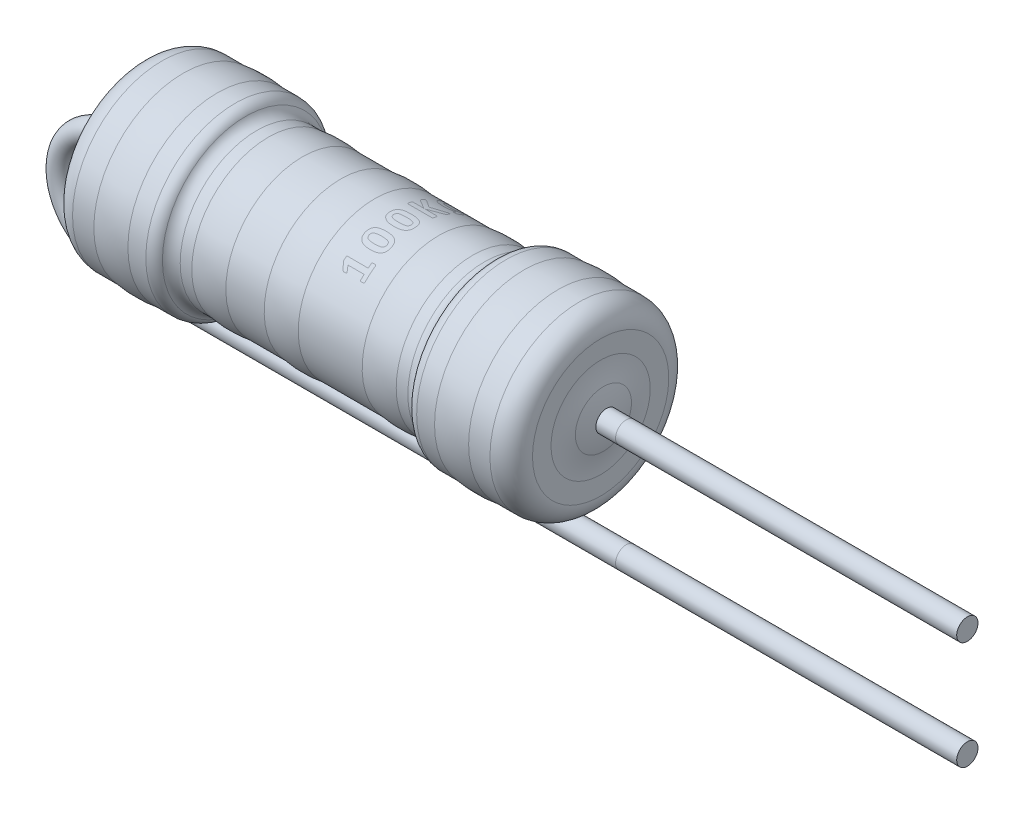
SolidWorks part; units mm, degrees
ref_plane "Front Plane" through (0, 0, 0) normal (0, 0, 1) x (1, 0, 0)
ref_plane "Top Plane" through (0, 0, 0) normal (0, 1, 0) x (1, 0, 0)
ref_plane "Right Plane" through (0, 0, 0) normal (1, 0, 0) x (0, 0, -1)
sketch "Sketch Set Wire Width" plane through (0, 0, 0) normal (0, 0, 1) x (1, 0, 0)
  line L0 (0, 0) -> (6, 0)
  line L1 (6, -2.54) -> (-6, -2.54)
  line L2 (6, 0) -> (14.0102, 0)
  line L3 (-6, 0) -> (-6, -2.54) construction
  line L4 (-6, 0) -> (-6, -2.54) construction
  line L5 (6, -2.54) -> (6, 0) construction
  line L6 (6, -2.54) -> (14.0102, -2.54)
  line L7 (14.0102, -2.54) -> (14.0102, 0) construction
  line L8 (-6, 0) -> (0, 0)
  arc A0 (-6, 0) -> (-6, -2.54) centre (-6, -1.27) ccw
  point P1 (0, 0)
  dimension "D2" = 2.54
  dimension "D3" = 30
  dimension "D1" = 12
  dimension "D4" = 6
sketch "Sketch Wire Diameter" plane through (0, 0, 0) normal (1, 0, 0) x (0, 0, -1)
  circle A0 centre (0, 0) radius 0.25
  dimension "D1" = 0.5
sweep "SET WIRE LENGTH" add profiles "Sketch Wire Diameter" path "Sketch Set Wire Width"
sketch "Sketch3" plane through (0, 0, 0) normal (0, 0, 1) x (1, 0, 0)
  line L0 (-5.4, 0) -> (5.4, 0)
  line L1 (0, 0) -> (0, 1.8) construction
  line L2 (-2.9, 1.8) -> (2.9, 1.8)
  line L3 (-5.4, 0) -> (-5.4, 1.6)
  line L4 (-4.9, 2.1) -> (-3.18, 2.1)
  line L5 (-2.9, 1.82) -> (-2.9, 1.8)
  line L6 (5.4, 0) -> (5.4, 1.6)
  line L7 (4.9, 2.1) -> (3.18, 2.1)
  line L8 (2.9, 1.82) -> (2.9, 1.8)
  arc A0 (-5.4, 1.6) -> (-4.9, 2.1) centre (-4.9, 1.6) cw
  arc A1 (5.4, 1.6) -> (4.9, 2.1) centre (4.9, 1.6) ccw
  arc A2 (-3.18, 2.1) -> (-2.9, 1.82) centre (-3.18, 1.82) cw
  arc A3 (3.18, 2.1) -> (2.9, 1.82) centre (3.18, 1.82) ccw
  dimension "D5" = 0.5
  dimension "D6" = 0.28
  dimension "D1" = 10.8
  dimension "D2" = 5.8
  dimension "D3" = 1.8
  dimension "D4" = 2.1
revolve "Revolve2" add sketch "Sketch3" angle 360 about L0
fillet "Fillet1" radius 0.3 2 edges at (2.9, 0, 1.8) (-2.9, 0, 1.8)
sketch "Sketch5" plane through (0, 0, 0) normal (0, 0, 1) x (1, 0, 0)
  line L0 (0, 0) -> (2, 0) construction
  line L1 (0, 0) -> (-0.3, 0) construction
  line L2 (-0.3, 0) -> (-2, 0) construction
  line L3 (-2, 0) -> (-4, 0) construction
  line L4 (2, 0) -> (4, 0) construction
  line L5 (-4, 0) -> (-4, 2.1) construction
  line L6 (-0.3, 0) -> (-0.3, 1.8) construction
  line L7 (-2, 0) -> (-2, 1.8) construction
  line L8 (2, 0) -> (2, 1.8) construction
  line L9 (4, 0) -> (4, 2.1) construction
  line L10 (-4, 2.1) -> (-4, 2.13) construction
  line L11 (-4.9, 2.1) -> (-3.18, 2.1) construction
  line L12 (4.9, 2.1) -> (3.18, 2.1) construction
  line L13 (-2.9, 1.8) -> (2.9, 1.8) construction
  line L14 (-2, 1.8) -> (-2, 1.83) construction
  line L17 (-4.4, 2.1) -> (-3.6, 2.1)
  line L19 (-5.4, 0) -> (5.4, 0) construction
  line L22 (-2.4, 1.8) -> (-1.6, 1.8) construction
  line L26 (-0.7, 1.8) -> (0.1, 1.8) construction
  line L30 (1.6, 1.8) -> (2.4, 1.8) construction
  line L34 (3.6, 2.1) -> (4.4, 2.1) construction
  line L36 (-0.3, 1.8) -> (-0.3, 1.83) construction
  line L37 (2, 1.8) -> (2, 1.83) construction
  line L38 (4, 2.1) -> (4, 2.13) construction
  arc A0 (-4.4, 2.1) -> (-3.6, 2.1) centre (-4, -0.5517) cw
  arc A1 (-2.4, 1.8) -> (-1.6, 1.8) centre (-2, -0.8517) cw construction
  arc A2 (-0.7, 1.8) -> (0.1, 1.8) centre (-0.3, -0.8517) cw construction
  arc A3 (1.6, 1.8) -> (2.4, 1.8) centre (2, -0.8517) cw construction
  arc A4 (3.6, 2.1) -> (4.4, 2.1) centre (4, -0.5517) cw construction
  dimension "D3" = 0.8
  dimension "D1" = 4
  dimension "D2" = 4
  dimension "D4" = 0.03
  dimension "D5" = 2
  dimension "D6" = 2
  dimension "D7" = 1.7
revolve "Band 1" add sketch "Sketch5" angle 360 about L2
sketch "Sketch8" plane through (0, 0, 0) normal (0, 0, 1) x (1, 0, 0)
  line L0 (-2.4, 1.8) -> (-1.6, 1.8) construction
  line L1 (-2.4, 1.8) -> (-1.6, 1.8)
  arc A0 (-1.6, 1.8) -> (-2.4, 1.8) centre (-2, -0.8517) ccw construction
  arc A1 (-1.6, 1.8) -> (-2.4, 1.8) centre (-2, -0.8517) ccw
revolve "Band 2" add sketch "Sketch8" angle 360 about L2
sketch "Sketch9" plane through (0, 0, 0) normal (0, 0, 1) x (1, 0, 0)
  line L0 (-0.7, 1.8) -> (0.1, 1.8) construction
  line L1 (-0.7, 1.8) -> (0.1, 1.8)
  arc A0 (0.1, 1.8) -> (-0.7, 1.8) centre (-0.3, -0.8517) ccw construction
  arc A1 (0.1, 1.8) -> (-0.7, 1.8) centre (-0.3, -0.8517) ccw
revolve "Band 3" add sketch "Sketch9" angle 360 about L2
sketch "Sketch10" plane through (0, 0, 0) normal (0, 0, 1) x (1, 0, 0)
  line L0 (1.6, 1.8) -> (2.4, 1.8) construction
  line L1 (1.6, 1.8) -> (2.4, 1.8)
  arc A0 (2.4, 1.8) -> (1.6, 1.8) centre (2, -0.8517) ccw construction
  arc A1 (2.4, 1.8) -> (1.6, 1.8) centre (2, -0.8517) ccw
revolve "Band 4" add sketch "Sketch10" angle 360 about L0
sketch "Sketch11" plane through (0, 0, 0) normal (0, 0, 1) x (1, 0, 0)
  line L0 (3.6, 2.1) -> (4.4, 2.1) construction
  line L1 (3.6, 2.1) -> (4.4, 2.1)
  arc A0 (4.4, 2.1) -> (3.6, 2.1) centre (4, -0.5517) ccw construction
  arc A1 (4.4, 2.1) -> (3.6, 2.1) centre (4, -0.5517) ccw
revolve "Band 5" add sketch "Sketch11" angle 360 about L4
sketch "Sketch12" plane through (0, 0, 0) normal (0, 0, 1) x (1, 0, 0)
  line L0 (-5.35, 0) -> (5.35, 0) construction
  line L1 (-5.35, 1) -> (-5.35, 0)
  line L2 (5.35, 1) -> (5.35, 0)
  line L3 (-5.35, 0) -> (-5.55, 0)
  line L4 (5.35, 0) -> (5.55, 0)
  arc A0 (-5.35, 1) -> (-5.55, 0) centre (-2.95, 0) ccw
  arc A1 (5.35, 1) -> (5.55, 0) centre (2.95, 0) cw
  dimension "D3" = 0.2
  dimension "D4" = 2.6
  dimension "D1" = 10.7
  dimension "D2" = 1
revolve "Revolve10" add sketch "Sketch12" angle 360 about L0
fillet "Fillet2" radius 2 2 edges at (5.4, 0, 0.8703) (-5.4, 0, -0.8703)
ref_plane "Plane2" through (0, 3, 0) normal (0, 1, 0) x (1, 0, 0)
sketch "Sketch13" plane through (0, 3, 0) normal (0, 1, 0) x (1, 0, 0)
  line L0 (0, 0) -> (1.15, 0) construction
  line L1 (1.15, 1.75) -> (1.15, -1.75) construction
  text T0 "100KΩ" font "Calibri" height 0.6
  dimension "D1" = 3.5
  dimension "D2" = 1.15
wrap "Wrap1" sketch "Sketch13" wrap type scribe source sketch "Sketch13" face at (0.1, 1.8, 0)
